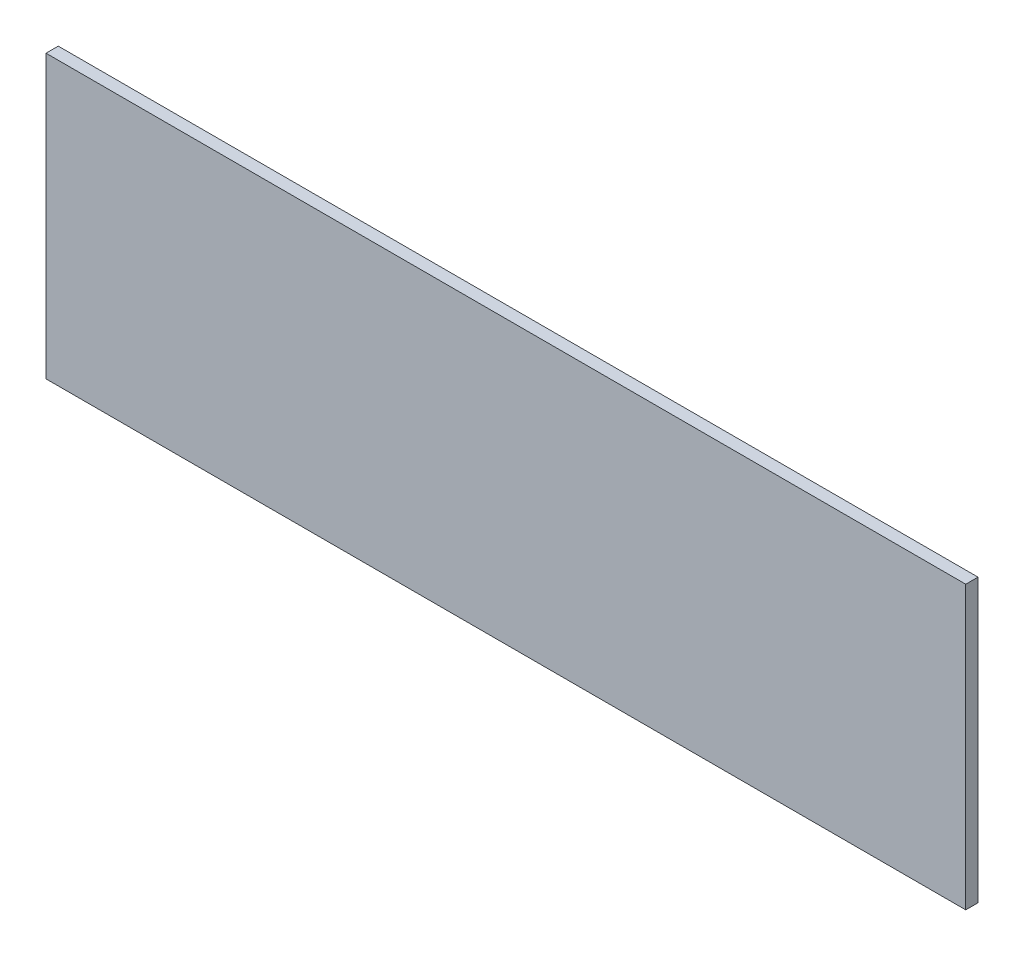
SolidWorks part; units mm, degrees
material "Pine"
ref_plane "Front Plane" through (0, 0, 0) normal (0, 0, 1) x (1, 0, 0)
ref_plane "Top Plane" through (0, 0, 0) normal (0, 1, 0) x (1, 0, 0)
ref_plane "Right Plane" through (0, 0, 0) normal (1, 0, 0) x (0, 0, -1)
sketch "Sketch1" plane through (0, 0, 0) normal (0, 0, 1) x (1, 0, 0)
  line L6 (0, 0) -> (900, 0)
  line L10 (0, 0) -> (0, 276)
  line L11 (0, 276) -> (900, 276)
  line L12 (900, 0) -> (900, 276)
  dimension "D3" = 276
  dimension "D1" = 900
extrude "Boss-Extrude1" add sketch "Sketch1" along normal blind 12 contours L10 L11 L12 L6
equation "\"LENGTH\" = 900mm"
equation "\"PLY\"= 12mm"
equation "\"D1@Sketch1\"=\"LENGTH\""
equation "\"D1@Boss-Extrude1\"=\"PLY\""
